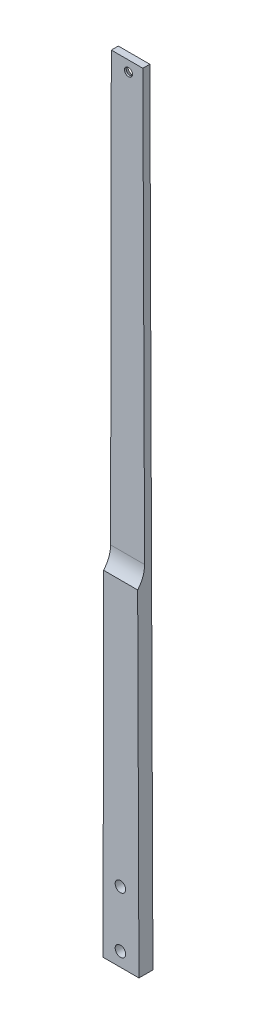
SolidWorks part; units mm, degrees
material "6061-T6 (SS)"
ref_plane "XY" through (0, 0, 0) normal (0, 0, 1) x (1, 0, 0)
ref_plane "XZ" through (0, 0, 0) normal (0, 1, 0) x (1, 0, 0)
ref_plane "YZ" through (0, 0, 0) normal (1, 0, 0) x (0, 0, -1)
ref_axis "X" through (-34.925, 0, 0) along (1, 0, 0)
ref_axis "Y" through (0, -53.3373, 0) along (0, 1, 0)
ref_axis "Z" through (0, 0, 6.6675) along (0, 0, -1)
sketch "Sketch1" plane through (0, 0, 0) normal (0, 0, 1) x (1, 0, 0)
  line L0 (-5.3354, 399.996) -> (10.3597, 399.996)
  line B0 (9.0464, 399.996) -> (-5.2871, 399.996)
  arc B1 (10.4977, 29.9643) -> (-5.8638, 31.2038) centre (0, 0) ccw
  spline B2 degree 3 poles (-5.2871, 399.996) (-5.392, 338.6022) (-5.5295, 254.0955) (-5.7181, 131.1648) (-5.8086, 69.6278) (-5.8638, 31.2038) knots 0 0 0 0 0.499418 0.687434 1 1 1 1
  spline B3 degree 3 poles (10.4977, 29.9643) (10.3579, 67.799) (10.0202, 157.8026) (9.6677, 247.8061) (9.323, 333.3153) (9.1861, 366.6557) (9.0464, 399.996) knots 0 0 0 0 0.306741 0.729696 0.729696 1 1 1 1
sketch_block_instance "Block2-3"
sketch_block "Block2"
sketch "Sketch2" plane through (0, 0, 0) normal (0, 0, 1) x (1, 0, 0)
  line L5 (-5.3354, 399.996) -> (10.3597, 399.996) construction
  line L6 (-5.2871, 399.996) -> (9.0464, 399.996)
  arc A1 (11.1829, 29.7154) -> (-6.1429, 31.1501) centre (0, 0) ccw construction
  arc A2 (10.4977, 29.9643) -> (-5.8638, 31.2038) centre (0, 0) ccw construction
  arc A3 (10.4977, 29.9643) -> (-5.8638, 31.2038) centre (0, 0) ccw
  spline S2 degree 3 poles (17.7702, -1970.0203) (14.5579, -1265.5276) (12.6307, -508.8588) (9.6677, 247.8061) (6.6351, 999.9719) (2.7265, 1699.9645) (-4.9943, 2399.9361) knots -5.4049 -5.4049 -5.4049 -5.4049 0.306741 0.729696 0.729696 6.404863 6.404863 6.404863 6.404863 only from (10.4977, 29.9643) to (9.0464, 399.996) construction
  spline S3 degree 3 poles (0.8769, 2399.9691) (-2.7293, 1671.9207) (-4.5067, 920.7552) (-6.741, -535.4974) (-7.3087, -1263.6973) (-8.5444, -1968.7825) knots -5.423052 -5.423052 -5.423052 -5.423052 0.499418 0.687434 6.423072 6.423072 6.423072 6.423072 only from (-5.2871, 399.996) to (-5.8638, 31.2038) construction
  spline S8 degree 3 poles (10.4977, 29.9643) (10.3579, 67.799) (10.0202, 157.8026) (9.6677, 247.8061) (9.323, 333.3153) (9.1861, 366.6557) (9.0464, 399.996) knots 0 0 0 0 0.306741 0.729696 0.729696 1 1 1 1
  spline S9 degree 3 poles (-5.2871, 399.996) (-5.392, 338.6022) (-5.5295, 254.0955) (-5.7181, 131.1648) (-5.8086, 69.6278) (-5.8638, 31.2038) knots 0 0 0 0 0.499418 0.687434 1 1 1 1
  point P0 (0, 0)
extrude "Boss-Extrude1" add sketch "Sketch2" along normal blind 6.35
sketch "Sketch3" plane through (0, 0, 0) normal (0, 0, 1) x (1, 0, 0)
  line L0 (0, 0) -> (2.032, 0) construction
  line L1 (-9.398, 0) -> (13.462, 0)
  line L2 (-9.398, 0) -> (-9.398, 44.45)
  line L3 (-9.398, 44.45) -> (13.462, 44.45)
  line L4 (13.462, 0) -> (13.462, 44.45)
  line L9 (2.032, 0) -> (2.032, 44.45) construction
  line L11 (13.462, 44.45) -> (-9.398, 44.45) construction
  circle A0 centre (0, 0) radius 31.75 construction
  dimension "D1" = 63.5
  dimension "D2" = 44.45
  dimension "D3" = 2.032
  dimension "D6" = 22.86
extrude "Cut-Extrude2" cut sketch "Sketch3" against normal through all and the other way through all
hole_wizard "3/16 (0.1875) Dowel Hole1" positions "Sketch4" profile "Sketch5" hole size "3/16" standard "ANSI Inch"
sketch "Sketch4" plane through (0, 0, 6.35) normal (0, 0, 1) x (1, 0, 0)
  line L0 (2.032, 44.45) -> (2.032, 50.8) construction
  line L2 (2.032, 50.8) -> (2.032, 76.2) construction
  line L4 (10.4441, 44.45) -> (-5.8447, 44.45) construction
  point P0 (2.032, 50.8)
  point P2 (2.032, 76.2)
  dimension "D1" = 6.35
  dimension "D2" = 25.4
  dimension "D3" = 2.032
sketch "Sketch5" plane through (2.032, 50.8, 6.35) normal (1, 0, 0) x (0, -1, 0)
  line L0 (0, 0) -> (0, 12.0988)
  line L1 (0, 12.0988) -> (2.3812, 10.668)
  line L2 (2.3812, 10.668) -> (2.3812, 0)
  line L5 (2.3812, 0) -> (0, 0)
  line L10 (0, 12.0988) -> (-2.3813, 10.668) construction
  line L11 (0, -6.35) -> (0, 107.95) construction
  dimension "Hole Dia." = 4.7625
  dimension "Hole Depth" = 10.668
  dimension "Drill Angle" = 118
hole_wizard "CSK for #6 Flat Head Socket Cap Screw1" positions "Sketch6" profile "Sketch7" countersink size "#6" standard "ANSI Inch" end condition through all
sketch "Sketch6" plane through (0, 0, 0) normal (0, 0, -1) x (-1, 0, 0)
  line L0 (-2.5122, 395.2335) -> (-2.5122, 399.996) construction
  line L1 (5.3354, 399.996) -> (-10.3597, 399.996) construction
  point P0 (-2.5122, 395.2335)
  dimension "D1" = 4.7625
sketch "Sketch7" plane through (2.5122, 395.2335, 0) normal (1, 0, 0) x (0, 1, 0)
  line L0 (0, 0) -> (0, 6.35)
  line L1 (0, 6.35) -> (1.8288, 6.35)
  line L2 (1.8288, 6.35) -> (1.8288, 2.3814)
  line L3 (1.8288, 2.3814) -> (3.8989, 0)
  line L5 (3.8989, 0) -> (0, 0)
  line L6 (-1.8288, 2.3814) -> (-3.8989, 0) construction
  line L11 (0, -6.35) -> (0, 107.95) construction
  dimension "Thru Hole Dia." = 3.6576
  dimension "Thru Hole Depth" = 6.35
  dimension "Near C'Sink Dia." = 7.7978
  dimension "Near C'Sink Angle" = 82
sketch "Sketch8" plane through (0, 0, 6.35) normal (0, 0, 1) x (1, 0, 0)
  line L0 (-5.3354, 399.996) -> (10.3597, 399.996) construction
  line L1 (-35.5509, 399.996) -> (52.4162, 399.996)
  line L2 (-35.5509, 399.996) -> (-35.5509, 196.796)
  line L3 (-35.5509, 196.796) -> (52.4162, 196.796)
  line L4 (52.4162, 399.996) -> (52.4162, 196.796)
  dimension "D1" = 203.2
extrude "Cut-Extrude3" cut sketch "Sketch8" against normal blind 3.175
fillet "Fillet1" radius 12.7 1 edges at (2.1243, 196.796, 3.175)
